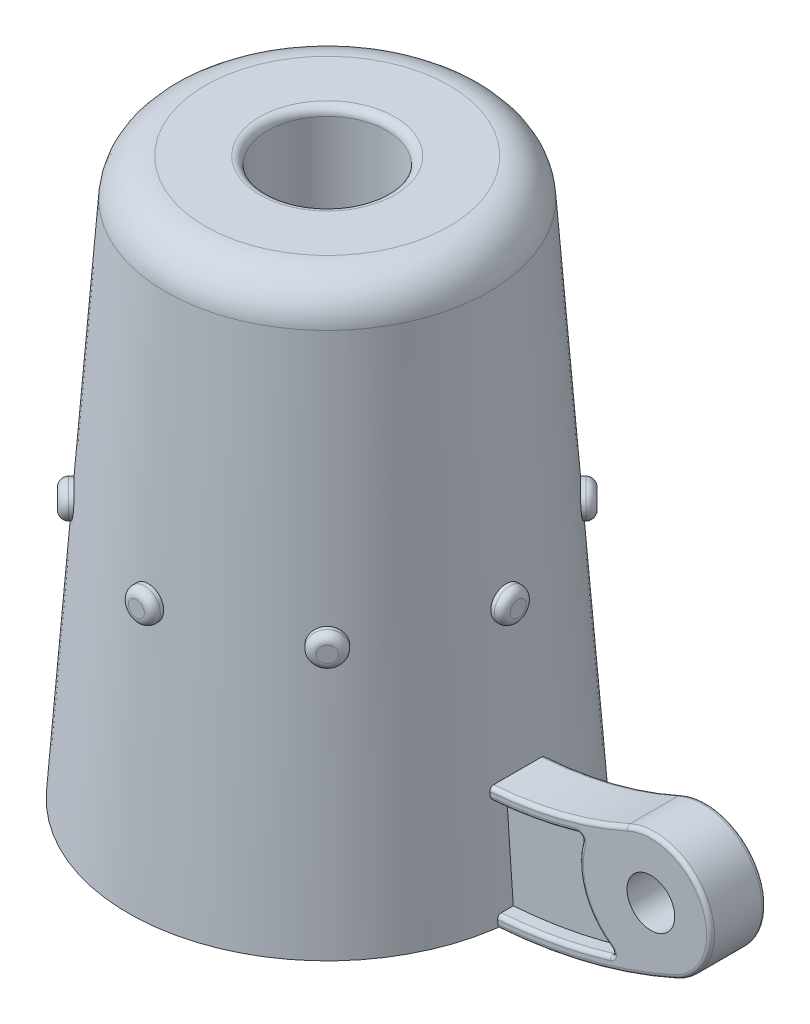
SolidWorks part; units mm, degrees
material "Copper"
ref_plane "Front Plane" through (0, 0, 0) normal (0, 0, 1) x (1, 0, 0)
ref_plane "Top Plane" through (0, 0, 0) normal (0, 1, 0) x (1, 0, 0)
ref_plane "Right Plane" through (0, 0, 0) normal (1, 0, 0) x (0, 0, -1)
sketch "Sketch1" plane through (0, 0, 0) normal (0, 0, 1) x (1, 0, 0)
  line L1 (0, 0) -> (-25, 0)
  line L3 (0, 0) -> (0, 70)
  line L4 (0, 70) -> (-20, 70)
  line L5 (-20, 70) -> (-25, 0)
revolve "Revolve1" add sketch "Sketch1" angle 360 about L3
fillet "Fillet1" radius 5 1 edges at (0, 70, -20)
sketch "Sketch2" plane through (0, 0, 0) normal (0, 0, 1) x (1, 0, 0)
  line L1 (23.9297, 14.9846) -> (24.9984, 0.0227)
  line L2 (25, 0) -> (20.3317, 65.3562) construction
  arc A2 (24.9984, 0.0227) -> (47.2809, 5.6571) centre (20.3317, 65.3562) ccw
  arc A5 (23.9297, 14.9846) -> (41.1093, 19.3286) centre (20.3317, 65.3562) ccw
  arc A6 (47.2809, 5.6571) -> (41.1093, 19.3286) centre (44.1951, 12.4928) ccw
extrude "Boss-Extrude1" add sketch "Sketch2" along normal blind 3.5 and the other way blind 3.5 separate body
sketch "Sketch3" plane through (0, 0, -3.5) normal (0, 0, -1) x (-1, 0, 0)
  circle A0 centre (-44.1951, 12.4928) radius 3
extrude "Cut-Extrude1" cut sketch "Sketch3" against normal blind 14.5
sketch "Sketch4" plane through (0, 0, -3.5) normal (0, 0, -1) x (-1, 0, 0)
  line L0 (-24.0365, 13.4884) -> (-24.8915, 1.5189)
  line L1 (-23.9297, 14.9846) -> (-24.9984, 0.0227) construction
  arc A3 (-39.0191, 4.1453) -> (-24.8915, 1.5189) centre (-20.3317, 65.3562) ccw
  arc A6 (-34.8792, 15.4326) -> (-24.0365, 13.4884) centre (-20.3317, 65.3562) ccw
  arc A7 (-39.1532, 5.0377) -> (-35.502, 14.8231) centre (-44.1951, 12.4928) ccw
  arc A8 (-34.8792, 15.4326) -> (-35.502, 14.8231) centre (-35.019, 14.9525) ccw
  arc A9 (-39.0191, 4.1453) -> (-39.1532, 5.0377) centre (-38.8731, 4.6235) cw
  dimension "D1" = 0.5
extrude "Cut-Extrude2" cut sketch "Sketch4" against normal blind 2
mirror "Mirror1" about plane through (0, 0, 0) normal (0, 0, 1) of "Cut-Extrude2"
sketch "Sketch5" plane through (0, 70, 0) normal (0, 1, 0) x (1, 0, 0)
  circle A0 centre (0, 0) radius 7.5
extrude "Cut-Extrude3" cut sketch "Sketch5" against normal blind 40
sketch "Sketch6" plane through (0, 0, 0) normal (0, -1, 0) x (1, 0, 0)
  circle A0 centre (0, 0) radius 18
extrude "Cut-Extrude4" cut sketch "Sketch6" against normal blind 40
fillet "Fillet2" radius 0.5 16 edges at (32.0293, 2.4343, 3.5) (39.3676, 4.5492, 3.5) (35.763, 9.3466, 3.5) (35.3688, 15.3099, 3.5) (32.0293, 2.4343, -3.5) (39.3676, 4.5492, -3.5) (35.763, 9.3466, -3.5) (35.3688, 15.3099, -3.5) (29.5095, 14.1726, 3.5) (29.5095, 14.1726, -3.5) (36.3887, 1.8549, -3.5) (32.7115, 16.3972, -3.5) (36.3887, 1.8549, 3.5) (32.7115, 16.3972, 3.5) (51.0309, 15.5786, -3.5) (51.0309, 15.5786, 3.5)
fillet "Fillet3" radius 1 1 edges at (0, 70, 7.5)
ref_plane "Plane1" through (0, 0, -24) normal (0, 0, 1) x (1, 0, 0)
sketch "Sketch7" plane through (0, 0, -24) normal (0, 0, 1) x (1, 0, 0)
  circle A0 centre (0, 32.6781) radius 2
extrude "Boss-Extrude2" add sketch "Sketch7" along normal up to surface (1.4226 mm away) up to face at (0, 65.3562, 20.3317)
pattern_circular "CirPattern1" count 8 every 45 about axis through (0, 70, 0) along (0, 1, 0) of "Boss-Extrude2" reverse direction yes
fillet "Fillet5" radius 1 8 edges at (24, 32.6781, 2) (-15.5563, 32.6781, -18.3848) (2, 32.6781, -24) (-18.3848, 32.6781, 15.5563) (-2, 32.6781, 24) (15.5563, 32.6781, 18.3848) (18.3848, 32.6781, -15.5563) (-24, 32.6781, -2)
